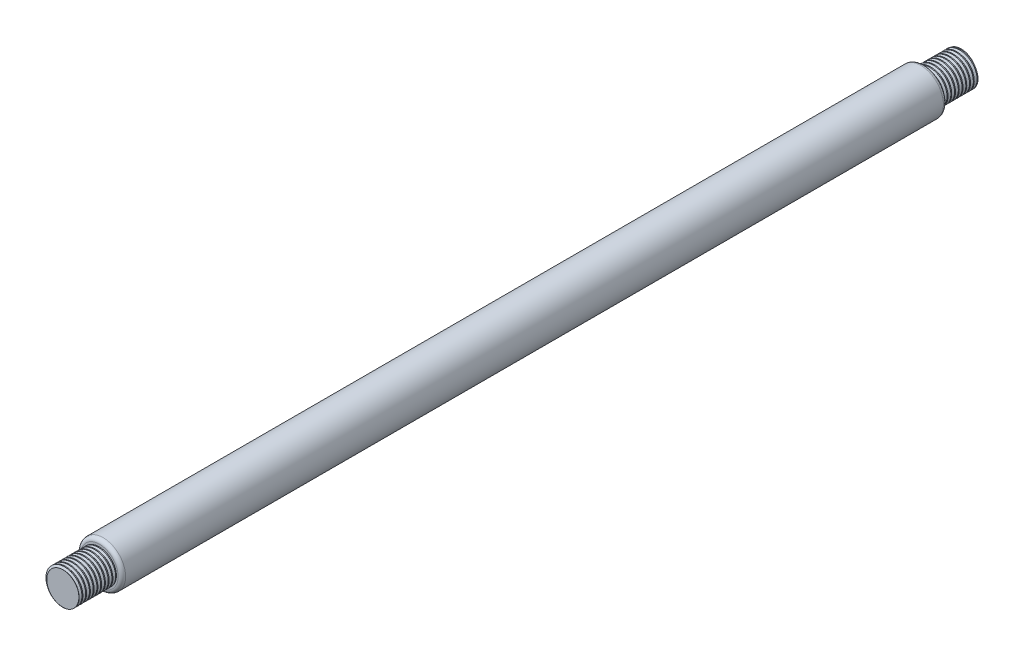
SolidWorks part; units mm, degrees
ref_plane "Front Plane" through (0, 0, 0) normal (0, 0, 1) x (1, 0, 0)
ref_plane "Top Plane" through (0, 0, 0) normal (0, 1, 0) x (1, 0, 0)
ref_plane "Right Plane" through (0, 0, 0) normal (1, 0, 0) x (0, 0, -1)
sketch "Sketch1" plane through (0, 0, 0) normal (1, 0, 0) x (0, 0, -1)
  line L0 (-58.3784, -7.7645) -> (61.6216, -7.7645)
  line L1 (61.6216, -7.7645) -> (61.6216, -1.7645)
  line L2 (61.6216, -1.7645) -> (-47.3784, -1.7645)
  line L3 (-48.3784, -2.7645) -> (-48.3784, -3.5145)
  line L4 (-48.6284, -3.7645) -> (-58.3784, -3.7645)
  line L5 (-58.3784, -3.7645) -> (-58.3784, -7.7645)
  arc A0 (-47.3784, -1.7645) -> (-48.3784, -2.7645) centre (-47.3784, -2.7645) ccw
  arc A1 (-48.3784, -3.5145) -> (-48.6284, -3.7645) centre (-48.6284, -3.5145) cw
  point P8 (-48.3784, -1.7645)
  point P11 (-48.3784, -3.7645)
  dimension "D6" = 1
  dimension "D7" = 0.25
  dimension "D1" = 120
  dimension "D2" = 4
  dimension "D3" = 6
  dimension "D4" = 2
  dimension "D5" = 10
revolve "Revolve1" add sketch "Sketch1" angle 360 about L0
thread "Thread1" pitch 1 start angle 0, offset 1, length 0, pitch 1, diameter 8
ref_plane "Plane1" through (-4, -7.7645, 59.3784) normal (0, 1, 0) x (1, 0, 0)
sketch "Thread Profile1" plane through (-4, -7.7645, 59.3784) normal (0, 1, 0) x (1, 0, 0)
  line L0 (0, 0) -> (0, 1) construction
  line L11 (0, 0) -> (0, 0.875)
  line L12 (0, 0.875) -> (-0.5413, 0.5625)
  line L13 (-0.5413, 0.5625) -> (-0.5413, 0.3125)
  line L15 (-0.5413, 0.3125) -> (0, 0)
  line L17 (-0.5413, 0.4375) -> (0, 0.4375) construction
  point P2 (0, 0)
  dimension "Pitch" = 1
  dimension "Profile_Angle" = 60
  dimension "Profile_Land" = 0.25
  dimension "Profile_Height" = 0.5413
ref_plane "Plane2" through (0, 0, 58.3784) normal (0, 0, -1) x (-1, 0, 0)
other "SurfaceCut2"
pattern_circular "CirPattern1" count 2 over 180 about axis through (0, -7.7645, -61.6216) along (0, 1, 0) of bodies 104
combine bodies "Combine1" bodies to combine 104 105
